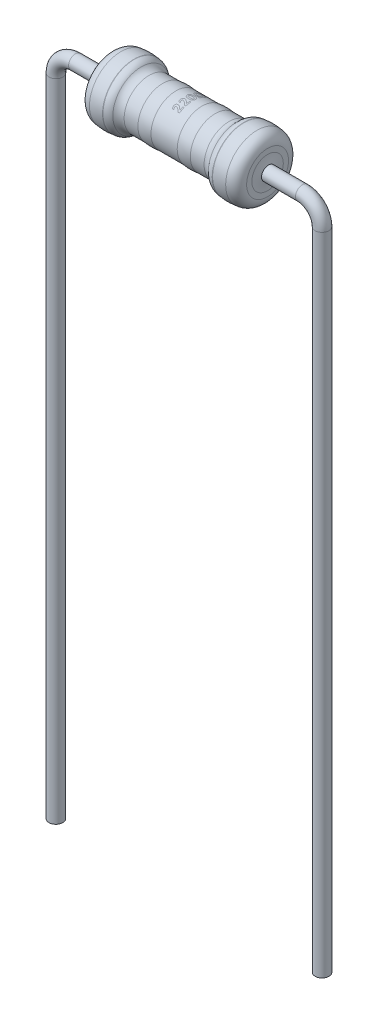
SolidWorks part; units mm, degrees
material "Plain Carbon Steel"
ref_plane "Front Plane" through (0, 0, 0) normal (0, 0, 1) x (1, 0, 0)
ref_plane "Top Plane" through (0, 0, 0) normal (0, 1, 0) x (1, 0, 0)
ref_plane "Right Plane" through (0, 0, 0) normal (1, 0, 0) x (0, 0, -1)
sketch "Sketch1" plane through (0, 0, 0) normal (0, 0, 1) x (1, 0, 0)
  line L0 (-4.33, 0) -> (4.33, 0)
  line L1 (-5.08, -0.75) -> (-5.08, -25.4)
  line L2 (5.08, -0.75) -> (5.08, -25.4)
  line L3 (-5.08, -25.4) -> (5.08, -25.4) construction
  line L4 (0, 0) -> (0, -25.4) construction
  arc A0 (-4.33, 0) -> (-5.08, -0.75) centre (-4.33, -0.75) ccw
  arc A1 (4.33, 0) -> (5.08, -0.75) centre (4.33, -0.75) cw
  dimension "D2" = 0.75
  dimension "D1" = 10.16
  dimension "D3" = 25.4
ref_plane "Plane1" through (-5.08, -25.4, 0) normal (0, -1, 0) x (-1, 0, 0)
sketch "Sketch2" plane through (-5.08, -25.4, 0) normal (0, -1, 0) x (-1, 0, 0)
  circle A0 centre (0, 0) radius 0.265
  dimension "D1" = 0.53
sweep "Sweep1" add profiles "Sketch2" path "Sketch1"
sketch "Sketch3" plane through (0, 0, 0) normal (0, 0, 1) x (1, 0, 0)
  line L0 (-3, 0) -> (3, 0)
  line L5 (-3, 0) -> (-3, 1.2)
  line L6 (3, 0) -> (3, 1.2)
  line L7 (-3, 1.2) -> (-1.75, 1.2)
  line L8 (3, 1.2) -> (1.75, 1.2)
  line L9 (-1.75, 1.2) -> (-1.75, 0.95)
  line L10 (-1.75, 0.95) -> (1.75, 0.95)
  line L11 (1.75, 0.95) -> (1.75, 1.2)
  line L12 (0, 0) -> (0, 0.95) construction
  dimension "D1" = 6
  dimension "D2" = 1.2
  dimension "D3" = 3.5
  dimension "D4" = 0.95
  dimension "D5" = 0.25
revolve "Revolve1" add sketch "Sketch3" angle 360 about L0
fillet "Fillet-1" radius 0.35 2 edges at (1.75, 0, 1.2) (-1.75, 0, 1.2)
fillet "Fillet-2" radius 0.4 4 edges at (3, 0, 1.2) (-3, 0, 1.2) (1.75, 0, 0.95) (-1.75, 0, 0.95)
sketch "Sketch5" plane through (0, 0, 0) normal (0, 0, 1) x (1, 0, 0)
  line L16 (-3, 0) -> (3, 0) construction
  line L17 (-2.6, 1.2) -> (-2.1, 1.2) construction
  line L18 (-2.6, 1.2) -> (-2.6, 0)
  line L19 (-2.6, 0) -> (-2.1, 0)
  line L20 (-2.1, 1.2) -> (-2.1, 0)
  line L21 (-1.75, 0.95) -> (1.75, 0.95) construction
  line L22 (2.6, 1.2) -> (2.1, 1.2) construction
  line L23 (2.6, 1.2) -> (2.6, 0)
  line L24 (2.6, 0) -> (2.1, 0)
  line L25 (2.1, 1.2) -> (2.1, 0)
  line L26 (-0.5, 0.95) -> (-1, 0.95) construction
  line L27 (-0.5, 0.95) -> (-0.5, 0)
  line L28 (-0.5, 0) -> (-1, 0)
  line L29 (-1, 0.95) -> (-1, 0)
  line L30 (-2.35, 1.2) -> (-2.35, 1.22) construction
  line L31 (1, 0.95) -> (0.5, 0.95) construction
  line L32 (1, 0.95) -> (1, 0)
  line L33 (1, 0) -> (0.5, 0)
  line L34 (0.5, 0.95) -> (0.5, 0)
  line L35 (-0.75, 0.95) -> (-0.75, 0.97) construction
  line L36 (0.75, 0.95) -> (0.75, 0.97) construction
  line L37 (2.35, 1.2) -> (2.35, 1.22) construction
  line L48 (-3, 0) -> (-3, 0.6)
  line L49 (-3, 0) -> (-3, 1.2) construction
  line L50 (-3, 0) -> (-3.05, 0)
  line L51 (-3.05, 0) -> (-3.05, 0.2)
  line L52 (3, 0) -> (3.05, 0)
  line L53 (3.05, 0) -> (3.05, 0.2)
  line L54 (3, 0) -> (3, 0.6)
  line L55 (3, 0) -> (3, 1.2) construction
  arc A0 (-2.6, 1.2) -> (-2.1, 1.2) centre (-2.35, -0.3525) cw
  arc A1 (-1, 0.95) -> (-0.5, 0.95) centre (-0.75, -0.6025) cw
  arc A2 (0.5, 0.95) -> (1, 0.95) centre (0.75, -0.6025) cw
  arc A3 (2.1, 1.2) -> (2.6, 1.2) centre (2.35, -0.3525) cw
  arc A6 (-3, 0.6) -> (-3.05, 0.2) centre (-4.625, 0.6) cw
  arc A7 (3.05, 0.2) -> (3, 0.6) centre (4.625, 0.6) cw
  dimension "D4" = 0.02
  dimension "D5" = 0.05
  dimension "D7" = 0.6
  dimension "D1" = 0.5
  dimension "D2" = 0.5
  dimension "D3" = 0.5
  dimension "D6" = 0.2
revolve "Revolve3" add sketch "Sketch5" angle 360 about L19
ref_plane "Plane2" through (0, 2, 0) normal (0, 1, 0) x (1, 0, 0)
sketch "Sketch6" plane through (0, 2, 0) normal (0, 1, 0) x (1, 0, 0)
  line L0 (0, 0) -> (0.15, 0) construction
  line L1 (0.15, 0.95) -> (0.15, -0.95) construction
  line L2 (0.5, 0.95) -> (-0.5, 0.95) construction
  text T0 "220Ω" font "Calibri" height 0.3
  dimension "D1" = 0.15
wrap "Wrap1" sketch "Sketch6" wrap type scribe source sketch "Sketch6" face at (-0.5, -0.95, 0)
